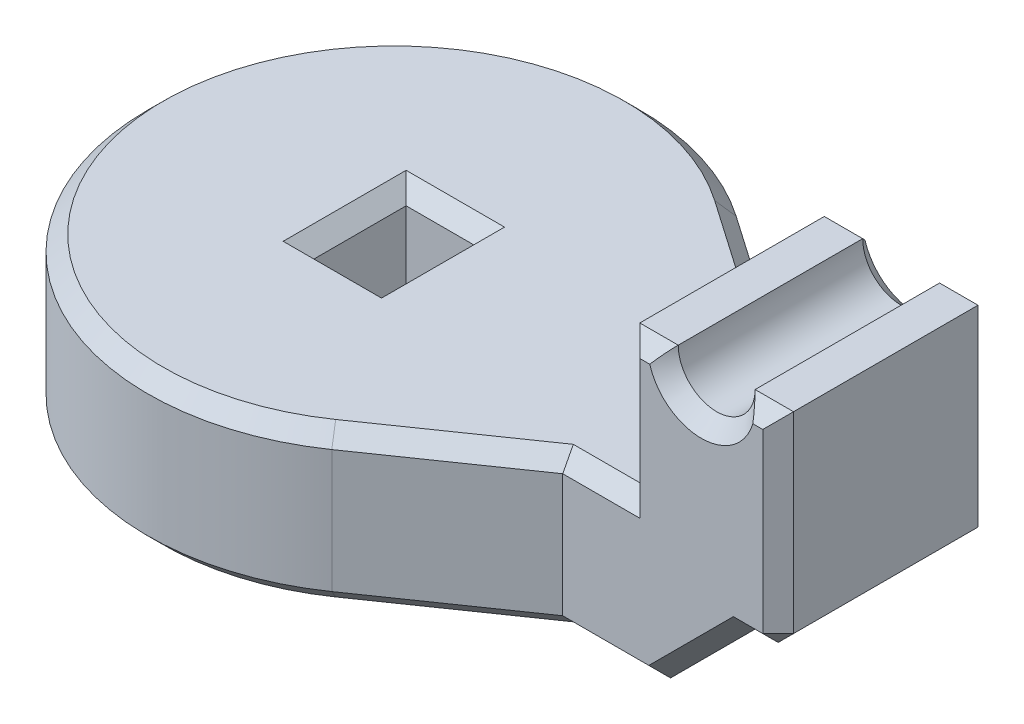
SolidWorks part; units mm, degrees
ref_plane "Front Plane" through (0, 0, 0) normal (0, 0, 1) x (1, 0, 0)
ref_plane "Top Plane" through (0, 0, 0) normal (0, 1, 0) x (1, 0, 0)
ref_plane "Right Plane" through (0, 0, 0) normal (1, 0, 0) x (0, 0, -1)
sketch "Sketch1" plane through (0, 0, 0) normal (0, 1, 0) x (1, 0, 0)
  line L2 (-998.0463, -3.5) -> (49001.9537, -3.5) construction
  line L3 (-998.5569, 3.5) -> (49001.4431, 3.5) construction
  line L4 (16, -1003.236) -> (16, 48996.764) construction
  line L5 (7.1937, 3.5) -> (16, 3.5)
  line L6 (16, 3.5) -> (16, -3.5)
  line L7 (16, -3.5) -> (7.1937, -3.5)
  line L9 (1.1, -1.5) -> (-1.1, -1.5)
  line L10 (1.1, -1.5) -> (1.1, 1.5)
  line L11 (1.1, 1.5) -> (-1.1, 1.5)
  line L12 (-1.1, -1.5) -> (-1.1, 1.5)
  line L13 (1.1, -1.5) -> (-1.1, 1.5) construction
  line L14 (1.1, 1.5) -> (-1.1, -1.5) construction
  arc A0 (-1.1, -1.0198) -> (1.1, -1.0198) centre (0, 0) ccw construction
  arc A1 (-1.1, 1.0198) -> (-1.1, -1.0198) centre (0, 0) ccw construction
  arc A2 (1.1, -1.0198) -> (1.1, 1.0198) centre (0, 0) ccw construction
  arc A3 (1.1, 1.0198) -> (-1.1, 1.0198) centre (0, 0) ccw construction
  arc A4 (7.1937, 3.5) -> (7.1937, -3.5) centre (0, 0) ccw
  arc A5 (7.1937, -3.5) -> (7.1937, 3.5) centre (0, 0) ccw construction
  point P19 (0, 1.5)
  dimension "D1" = 3
  dimension "D4" = 16
  dimension "D2" = 1.1
  dimension "D5" = 3.5
  dimension "D6" = 3.5
  dimension "D7" = 16
extrude "Boss-Extrude1" add sketch "Sketch1" against normal blind 5
sketch "Sketch3" plane through (0, 0, 0) normal (0, 1, 0) x (1, 0, 0)
  line L0 (7.1937, -3.5) -> (16, -3.5) construction
  line L1 (16, 3.5) -> (11, 3.5)
  line L2 (16, 3.5) -> (16, -3.5)
  line L3 (16, -3.5) -> (11, -3.5)
  line L4 (11, 3.5) -> (11, -3.5)
  dimension "D1" = 11
extrude "Boss-Extrude2" add sketch "Sketch3" along normal blind 1.5
sketch "Sketch6" plane through (0, -5, 0) normal (0, -1, 0) x (1, 0, 0)
  line L0 (7.1937, 3.5) -> (16, 3.5) construction
  line L1 (16, -3.5) -> (12, -3.5)
  line L2 (16, -3.5) -> (16, 3.5)
  line L3 (16, 3.5) -> (12, 3.5)
  line L4 (12, -3.5) -> (12, 3.5)
  line L6 (16, -3.5) -> (7.1937, -3.5) construction
  line L7 (16, 3.5) -> (16, -3.5) construction
  dimension "D1" = 12
extrude "Cut-Extrude1" cut sketch "Sketch6" against normal blind 2.75
chamfer "Chamfer2" distance 2.75 angle 45 1 edges at (12, -2.25, 0)
sketch "Sketch7" plane through (0, 1.5, 0) normal (0, 1, 0) x (1, 0, 0)
  line L0 (16, 3.5) -> (11, 3.5) construction
  line L1 (11, 3.5) -> (16, 3.5)
  line L2 (11, 3.5) -> (11, -3.5)
  line L3 (11, -3.5) -> (16, -3.5)
  line L4 (16, 3.5) -> (16, -3.5)
extrude "Boss-Extrude3" add sketch "Sketch7" along normal blind 3
sketch "Sketch8" plane through (0, 0, -3.5) normal (0, 0, -1) x (-1, 0, 0)
  line L0 (-16, 4.5) -> (-11, 4.5) construction
  line L1 (-12.25, 4.5) -> (-14.75, 4.5)
  arc A0 (-14.75, 4.5) -> (-12.25, 4.5) centre (-13.5, 4.5) ccw
  arc A1 (-12.25, 4.5) -> (-14.75, 4.5) centre (-13.5, 4.5) ccw construction
  dimension "D1" = 2.5
extrude "Cut-Extrude2" cut sketch "Sketch8" against normal through all
sketch "Sketch9" plane through (0, -5, 0) normal (0, -1, 0) x (1, 0, 0)
  line L0 (7.1937, -3.5) -> (8.9937, -3.5)
  line L1 (12, -3.5) -> (7.1937, -3.5) construction
  line L2 (8.9937, -3.5) -> (4.5573, -6.575)
  line L3 (8.9937, -3.5) -> (8.9937, 3.5) construction
  line L4 (7.1937, 3.5) -> (12, 3.5) construction
  line L5 (7.1937, 3.5) -> (8.9937, 3.5)
  line L6 (8.9937, 3.5) -> (4.5573, 6.575)
  arc A0 (4.5573, -6.575) -> (7.1937, -3.5) centre (0, 0) ccw
  arc A1 (7.1937, 3.5) -> (7.1937, -3.5) centre (0, 0) ccw construction
  arc A2 (4.5573, 6.575) -> (4.5573, -6.575) centre (0, 0) ccw construction
  arc A3 (7.1937, -3.5) -> (7.1937, 3.5) centre (0, 0) ccw construction
  arc A4 (7.1937, 3.5) -> (4.5573, 6.575) centre (0, 0) ccw
  dimension "D1" = 1.8
extrude "Boss-Extrude4" add sketch "Sketch9" against normal up to surface (5 mm away) up to face at (5.2984, 0, 0)
chamfer "Chamfer3" distance 0.5 angle 45 33 edges at (0, -5, 1.5) (-1.1, -5, 0) (0, -5, -1.5) (1.1, -5, 0) (0, 0, 1.5) (1.1, 0, 0) (0, 0, -1.5) (-1.1, 0, 0) (15.375, 4.5, 3.5) (13.5, 3.25, 3.5) (11.625, 4.5, 3.5) (16, -2.25, 0) (16, 1.125, 3.5) (15.375, -2.25, 3.5) (13.375, -3.625, 3.5) (10.4969, -5, 3.5) (-8, -5, 0) (10.4969, -5, -3.5) (13.375, -3.625, -3.5) (15.375, -2.25, -3.5) (16, 1.125, -3.5) (15.375, 4.5, -3.5) (13.5, 3.25, -3.5) (11.625, 4.5, -3.5) (11, 2.25, 3.5) (9.9969, 0, 3.5) (-8, 0, 0) (11, 2.25, -3.5) (9.9969, 0, -3.5) (6.7755, -5, -5.0375) (6.7755, -5, 5.0375) (6.7755, 0, -5.0375) (6.7755, 0, 5.0375)
